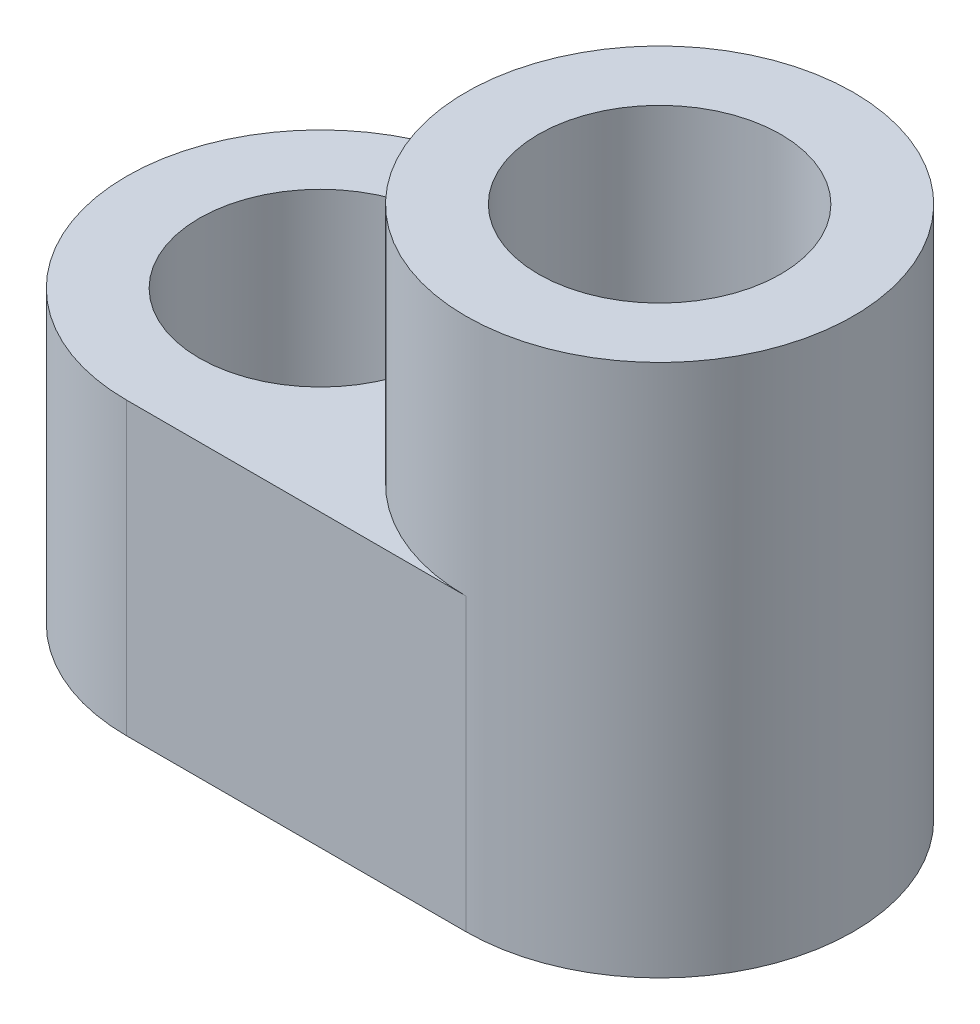
SolidWorks part; units mm, degrees
ref_plane "Front Plane" through (0, 0, 0) normal (0, 0, 1) x (1, 0, 0)
ref_plane "Top Plane" through (0, 0, 0) normal (0, 1, 0) x (1, 0, 0)
ref_plane "Right Plane" through (0, 0, 0) normal (1, 0, 0) x (0, 0, -1)
sketch "Sketch1" plane through (0, 0, 0) normal (0, 1, 0) x (1, 0, 0)
  line L1 (-7.5, -4) -> (7.5, -4)
  line L2 (-7.5, -4) -> (-7.5, 4)
  line L3 (-7.5, 4) -> (7.5, 4)
  line L4 (7.5, -4) -> (7.5, 4)
  line L5 (-7.5, -4) -> (7.5, 4) construction
  line L6 (-7.5, 4) -> (7.5, -4) construction
  circle A0 centre (-3.5, 0) radius 2.5
  circle A1 centre (3.5, 0) radius 2.5
  point P0 (0, 0)
  dimension "D1" = 15
  dimension "D2" = 3.5
  dimension "D3" = 3.5
  dimension "D4" = 8
extrude "Boss-Extrude1" add sketch "Sketch1" along normal blind 6
fillet "Fillet1" radius 4 4 edges at (-7.5, 3, -4) (7.5, 3, -4) (7.5, 3, 4) (-7.5, 3, 4)
sketch "Sketch2" plane through (0, 6, 0) normal (0, 1, 0) x (1, 0, 0)
  circle A2 centre (3.5, 0) radius 4
  circle A3 centre (3.5, 0) radius 4
  dimension "D1" = 1.5
extrude "Boss-Extrude2" add sketch "Sketch2" along normal blind 5
sketch "Sketch4" plane through (0, 6, 0) normal (0, -1, 0) x (1, 0, 0)
  circle A1 centre (3.5, 0) radius 2.5
extrude "Cut-Extrude1" cut sketch "Sketch4" against normal blind 25
